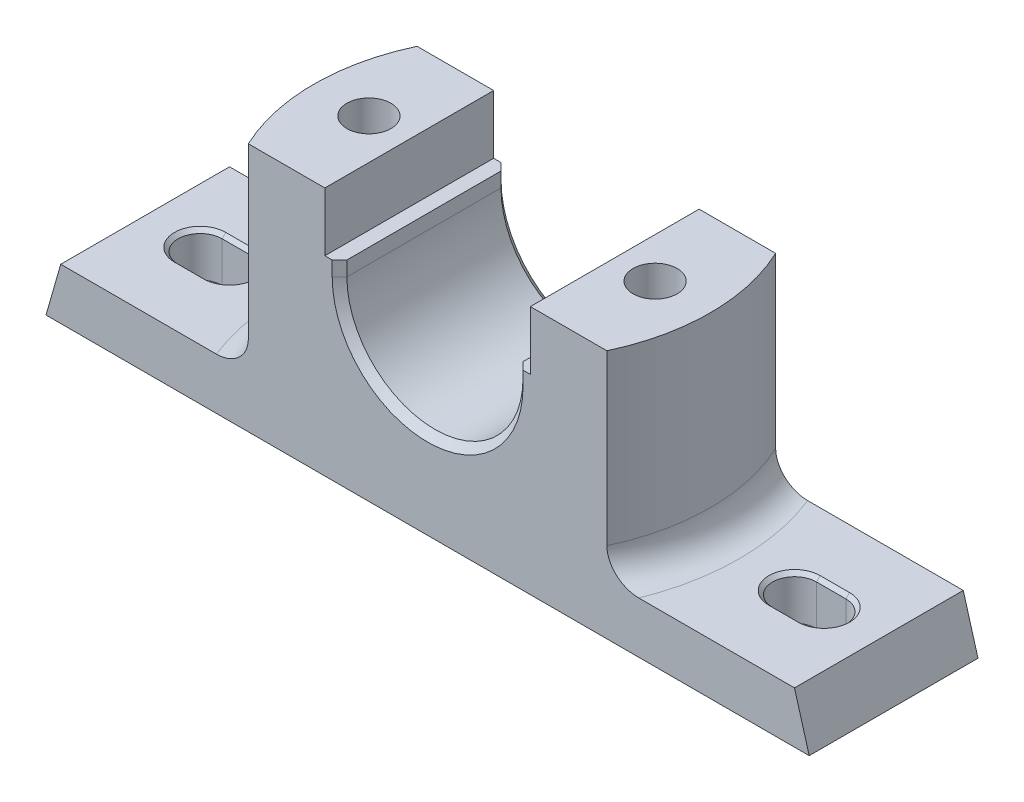
SolidWorks part; units mm, degrees
ref_plane "Front Plane" through (0, 0, 0) normal (0, 0, 1) x (1, 0, 0)
ref_plane "Top Plane" through (0, 0, 0) normal (0, 1, 0) x (1, 0, 0)
ref_plane "Right Plane" through (0, 0, 0) normal (1, 0, 0) x (0, 0, -1)
sketch "Sketch1" plane through (0, 0, 0) normal (0, 0, 1) x (1, 0, 0)
  line L0 (0, 0) -> (0, -37999.4348) construction
  line L1 (0, 0) -> (-37999.4348, 0) construction
  line L2 (-104, 0) -> (104, 0)
  line L3 (-104, 0) -> (-99.9856, 14)
  line L4 (-99.9856, 14) -> (-54, 14)
  line L5 (-54, 14) -> (-54, 68)
  line L6 (-54, 68) -> (-28, 68)
  line L7 (-28, 68) -> (-28, 52)
  line L8 (-28, 52) -> (-24, 52)
  line L9 (-24, 52) -> (-24, 48)
  line L10 (24, 52) -> (24, 48)
  line L11 (28, 52) -> (24, 52)
  line L12 (28, 68) -> (28, 52)
  line L13 (54, 68) -> (28, 68)
  line L14 (54, 14) -> (54, 68)
  line L15 (99.9856, 14) -> (54, 14)
  line L16 (104, 0) -> (99.9856, 14)
  arc A0 (-24, 48) -> (24, 48) centre (0, 48) ccw
  point P8 (0, 0)
  point P14 (0, 0)
  dimension "D2" = 106
  dimension "D6" = 16
  dimension "D7" = 24
  dimension "D1" = 208
  dimension "D3" = 14
  dimension "D4" = 68
  dimension "D5" = 56
  dimension "D8" = 4
  dimension "D9" = 108
extrude "Boss-Extrude1" add sketch "Sketch1" along normal mid plane 46
sketch "Sketch3" plane through (0, 14, 0) normal (0, 1, 0) x (1, 0, 0)
  line L0 (-54, 23) -> (-48.8569, 23)
  line L1 (-28, 23) -> (-54, 23) construction
  line L2 (-54, -23) -> (-48.8569, -23)
  line L3 (-28, -23) -> (-54, -23) construction
  line L4 (-54, -23) -> (-54, 23)
  line L5 (0, 0) -> (-50000, 0) construction
  line L6 (0, 0) -> (0, -50000) construction
  line L7 (54, -23) -> (54, 23)
  line L8 (54, -23) -> (48.8569, -23)
  line L9 (54, 23) -> (48.8569, 23)
  arc A0 (-48.8569, 23) -> (-48.8569, -23) centre (0, 0) ccw
  arc A1 (48.8569, 23) -> (48.8569, -23) centre (0, 0) cw
  line M6 (-54, -23) -> (-54, 23)
  dimension "D1" = 108
extrude "Cut-Extrude1" cut sketch "Sketch3" along normal blind 76 contours A0 L0 L4 | A0 L2 M6 | L7 A1 L8 | L9 A1 L7 region at (-52.4705, 14, 17.3062) region at (-52.4705, 14, -17.3062) region at (52.4705, 14, 17.3062) region at (52.4705, 14, -17.3062)
chamfer "Chamfer1" distance 2 angle 45 6 edges at (24, 50, -23) (-24, 50, -23) (0, 24, -23) (24, 50, 23) (-24, 50, 23) (0, 24, 23)
sketch "Sketch4" plane through (0, 68, 0) normal (0, 1, 0) x (1, 0, 0)
  line L0 (0, 0) -> (-50000, 0) construction
  line L1 (0, 0) -> (0, -50000) construction
  line L2 (-85, 0) -> (-77, 0) construction
  line L3 (-85, 6) -> (-77, 6)
  line L4 (-85, -6) -> (-77, -6)
  line L5 (85, 0) -> (77, 0) construction
  line L6 (85, 6) -> (77, 6)
  line L7 (85, -6) -> (77, -6)
  line L8 (53, -14) -> (25, -14)
  line L9 (-53, 14) -> (-25, 14)
  line L10 (-53, 14) -> (-53, -14)
  line L11 (-53, -14) -> (-25, -14)
  line L12 (-25, 14) -> (-25, -14)
  line L13 (-39, -14) -> (-39, 14) construction
  line L14 (-53, 0) -> (-25, 0) construction
  line L15 (25, 14) -> (25, -14)
  line L16 (53, 14) -> (25, 14)
  line L17 (53, 14) -> (53, -14)
  line L19 (-97.5, 17.5) -> (97.5, 17.5)
  line L20 (-97.5, 17.5) -> (-97.5, -17.5)
  line L21 (-97.5, -17.5) -> (97.5, -17.5)
  line L22 (97.5, 17.5) -> (97.5, -17.5)
  line L23 (0, -17.5) -> (0, 17.5) construction
  line L24 (-97.5, 0) -> (97.5, 0) construction
  circle A0 centre (-39, 0) radius 6
  circle A1 centre (39, 0) radius 6
  arc A2 (-85, 6) -> (-85, -6) centre (-85, 0) ccw
  arc A3 (-77, -6) -> (-77, 6) centre (-77, 0) ccw
  arc A4 (85, 6) -> (85, -6) centre (85, 0) cw
  arc A5 (77, -6) -> (77, 6) centre (77, 0) cw
  point P11 (-81, 0)
  point P18 (81, 0)
  point P33 (0, 0)
  point P37 (0, 0)
  arc M16 (-48.8569, 23) -> (-48.8569, -23) centre (0, 0) ccw
  line M18 (-28, -23) -> (-28, 23)
  dimension "D1" = 78
  dimension "D2" = 12
  dimension "D3" = 12
  dimension "D4" = 8
  dimension "D5" = 154
  dimension "D6" = 28
  dimension "D7" = 35
  dimension "D8" = 195
extrude "Cut-Extrude2" cut sketch "Sketch4" along normal blind 2 from surface contours L20 L21 L11 L10 L9 L19 A3 L4 A2 L3 M16 | L11 L9 L10 A0 M16 M18 | A0 | L4 A3 L3 A2 | L21 L11 M16 M18 | L19 L9 M16 M18 | L22 L19 L9 L12 L11 L21 L16 L17 L8 L15 L7 A5 L6 A4 M18 | L10 L11 M16 | L10 M16 | L9 L10 M16 | L12 L9 L11 M18 | A5 L7 A4 L6 | L17 L16 L15 L8 A1 | A1 region at (-81, 68, 0) region at (81, 68, 0) region at (39, 68, 13.604) region at (-53.5813, 68, -12.172) region at (-52.725, 68, -12.8151) region at (-39.8226, 68, -15.7368) region at (-40.0768, 68, -13.6246) region at (-53.4003, 68, 0) region at (-26.6971, 68, -15.75) region at (-26.5, 68, 0) region at (-52.725, 68, 12.8151) region at (-39.8226, 68, 15.7368) region at (-39, 68, 0) region at (39, 68, 0) starting at face at (0, 0, 0)
extrude "Cut-Extrude3" cut sketch "Sketch4<3>" against normal through all contours A0 | A1 | L4 A3 L3 A2 | A5 L7 A4 L6 region at (-81, 68, 0) region at (81, 68, 0) region at (-39, 68, 0) region at (39, 68, 0)
sketch "Sketch4<3>" plane through (0, 68, 0) normal (0, 1, 0) x (1, 0, 0) same geometry as "Sketch4"
extrude "Cut-Extrude4" cut sketch "Sketch4<4>" along normal blind 10 from surface contours L11 L9 L10 A0 M16 M18 | L17 L16 L15 L8 A1 | A0 | A1 region at (39, 68, 13.604) region at (-40.0768, 68, -13.6246) region at (-39, 68, 0) region at (39, 68, 0) starting at face at (0, 2, 0)
sketch "Sketch4<4>" plane through (0, 68, 0) normal (0, 1, 0) x (1, 0, 0) same geometry as "Sketch4"
chamfer "Chamfer2" distance 1 angle 45 8 edges at (71, 14, 0) (81, 14, 6) (81, 14, -6) (91, 14, 0) (-91, 14, 0) (-81, 14, -6) (-81, 14, 6) (-71, 14, 0)
fillet "Fillet1" radius 8 2 edges at (-54, 14, 0) (54, 14, 0)
